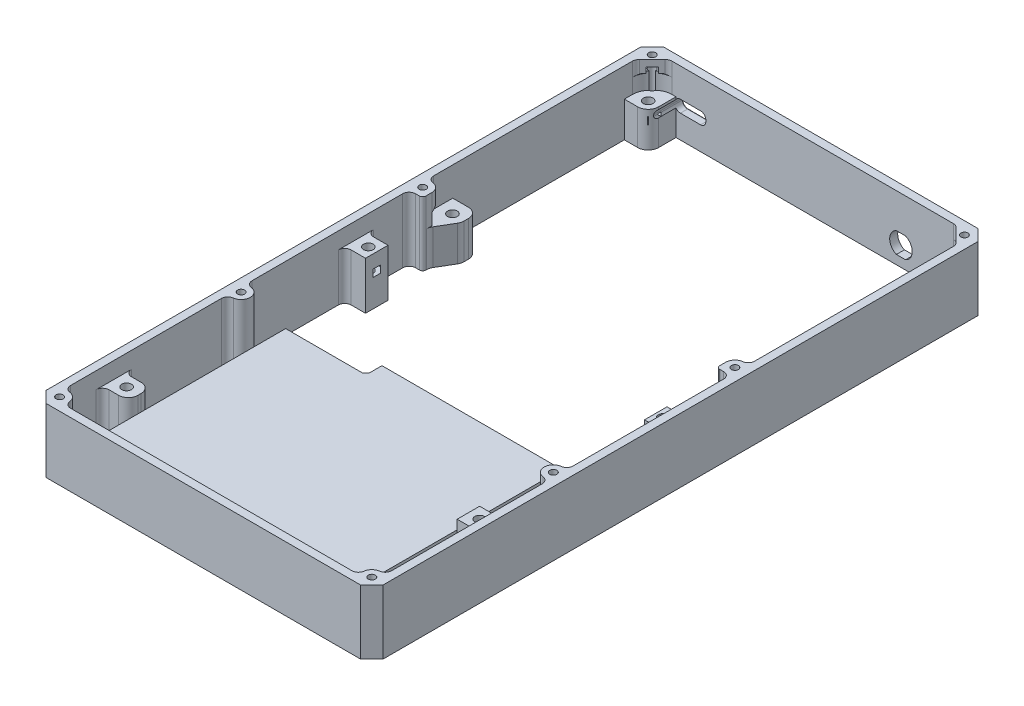
SolidWorks part; units mm, degrees
note: The reader was unsure of these and kept them because the rebuilt part matched: shared geometry of "Sketch1<3>", "Sketch9<3>", "Sketch11<5>".
material "Rubber"
ref_plane "Front Plane" through (0, 0, 0) normal (0, 0, 1) x (1, 0, 0)
ref_plane "Top Plane" through (0, 0, 0) normal (0, 1, 0) x (1, 0, 0)
ref_plane "Right Plane" through (0, 0, 0) normal (1, 0, 0) x (0, 0, -1)
sketch "Sketch1" plane through (0, 0, 0) normal (0, 1, 0) x (1, 0, 0)
  line L0 (0, 0) -> (0, -3.5) construction
  line L1 (0, -3.5) -> (3.5, 0)
  line L2 (3.5, 0) -> (0, 0) construction
  line L3 (3.5, 0) -> (101.5, 0)
  line L4 (101.5, 0) -> (105, -3.5)
  line L5 (105, -3.5) -> (105, -188.8454)
  line L6 (105, -188.8454) -> (101.5, -192.3454)
  line L7 (101.5, -192.3454) -> (3.5, -192.3454)
  line L8 (3.5, -192.3454) -> (0, -188.8454)
  line L9 (0, -188.8454) -> (0, -3.5)
  line L12 (1.75, -1.75) -> (3.8713, -3.8713) construction
  line L13 (103.25, -1.75) -> (101.1287, -3.8713) construction
  line L14 (1.75, -190.5954) -> (3.8713, -188.4741) construction
  line L15 (103.25, -190.5954) -> (101.1287, -188.4741) construction
  line L16 (3.8713, -188.4741) -> (3.8713, -131.9227) construction
  line L17 (3.8713, -131.9227) -> (3.8713, -75.3713) construction
  line L18 (3.8713, -75.3713) -> (3.8713, -3.8713) construction
  line L32 (2.5, -185.9757) -> (2.5, -134.4211)
  line L34 (6.3697, -2.5) -> (98.6303, -2.5)
  line L36 (102.5, -6.3697) -> (102.5, -72.8729)
  line L38 (98.6303, -189.8454) -> (6.3697, -189.8454)
  line L40 (2.5, -187.8099) -> (2.5, -4.5355) construction
  line L41 (4.5355, -189.8454) -> (2.5, -187.8099) construction
  line L42 (100.4645, -189.8454) -> (4.5355, -189.8454) construction
  line L43 (102.5, -187.8099) -> (100.4645, -189.8454) construction
  line L44 (102.5, -4.5355) -> (102.5, -187.8099) construction
  line L45 (102.5, -134.4211) -> (102.5, -185.9757)
  line L46 (102.5, -77.8697) -> (102.5, -129.4243)
  line L47 (2.5, -4.5355) -> (4.5355, -2.5) construction
  line L48 (100.4645, -2.5) -> (102.5, -4.5355) construction
  line L49 (4.5355, -2.5) -> (100.4645, -2.5) construction
  line L50 (2.5, -72.8729) -> (2.5, -6.3697)
  line L51 (2.5, -129.4243) -> (2.5, -77.8697)
  line L52 (52.5, 0) -> (52.5, -192.3454) construction
  line L53 (6.6657, -65.633) -> (2.5, -65.633)
  line L54 (6.7213, -76.1515) -> (10.4157, -69.9096)
  line L55 (98.2787, -76.1515) -> (94.5843, -69.9096)
  line L56 (98.3343, -65.633) -> (102.5, -65.633)
  line L57 (6.6657, -11.173) -> (2.5, -11.173)
  line L58 (98.3343, -11.173) -> (102.5, -11.173)
  line L59 (9.9157, -7.923) -> (9.9157, -2.5)
  line L60 (95.0843, -7.923) -> (95.0843, -2.5)
  line L61 (6.6657, -68.883) -> (9.8928, -70.793) construction
  line L62 (98.3343, -68.883) -> (95.1072, -70.793) construction
  line L63 (94.5843, -69.9096) -> (94.5843, -65.633)
  line L64 (94.5843, -65.633) -> (98.3343, -65.633)
  line L65 (2.5, -64.633) -> (10.4157, -64.633)
  line L66 (10.4157, -69.9096) -> (10.4157, -64.633)
  line L67 (94.5843, -65.633) -> (94.5843, -64.633)
  line L68 (94.5843, -64.633) -> (102.5, -64.633)
  line L69 (98.2787, -76.1515) -> (98.2787, -78.2213)
  line L70 (6.7213, -78.2213) -> (2.5, -78.2213)
  line L71 (6.7213, -76.1515) -> (6.7213, -75.3713)
  line L72 (98.2787, -78.2213) -> (102.5, -78.2213)
  line L73 (6.7213, -76.1515) -> (6.7213, -78.2213)
  line L74 (98.2787, -76.1515) -> (98.2787, -75.3713)
  circle A0 centre (3.8713, -3.8713) radius 1.1
  circle A1 centre (101.1287, -3.8713) radius 1.1
  circle A2 centre (3.8713, -188.4741) radius 1.1
  circle A3 centre (101.1287, -188.4741) radius 1.1
  circle A4 centre (3.8713, -131.9227) radius 1.1
  circle A6 centre (101.1287, -131.9227) radius 1.1
  circle A8 centre (3.8713, -75.3713) radius 1.1
  circle A9 centre (101.1287, -75.3713) radius 1.1
  arc A10 (2.5, -134.4211) -> (2.5, -129.4243) centre (3.8713, -131.9227) ccw
  arc A11 (2.5, -77.8697) -> (2.5, -72.8729) centre (3.8713, -75.3713) ccw
  arc A12 (2.5, -6.3697) -> (6.3697, -2.5) centre (3.8713, -3.8713) ccw
  arc A13 (98.6303, -2.5) -> (102.5, -6.3697) centre (101.1287, -3.8713) ccw
  arc A14 (102.5, -72.8729) -> (102.5, -77.8697) centre (101.1287, -75.3713) ccw
  arc A15 (102.5, -129.4243) -> (102.5, -134.4211) centre (101.1287, -131.9227) ccw
  arc A16 (102.5, -185.9757) -> (98.6303, -189.8454) centre (101.1287, -188.4741) ccw
  arc A17 (6.3697, -189.8454) -> (2.5, -185.9757) centre (3.8713, -188.4741) ccw
  circle A18 centre (3.8713, -188.4741) radius 2.85 construction
  circle A19 centre (101.1287, -188.4741) radius 2.85 construction
  circle A20 centre (101.1287, -131.9227) radius 2.85 construction
  circle A21 centre (101.1287, -75.3713) radius 2.85 construction
  circle A22 centre (101.1287, -3.8713) radius 2.85 construction
  circle A23 centre (3.8713, -3.8713) radius 2.85 construction
  circle A24 centre (3.8713, -75.3713) radius 2.85 construction
  circle A25 centre (3.8713, -131.9227) radius 2.85 construction
  circle A28 centre (6.6657, -68.883) radius 1.5
  circle A29 centre (6.6657, -7.923) radius 1.5
  circle A30 centre (98.3343, -68.883) radius 1.5
  circle A31 centre (98.3343, -7.923) radius 1.5
  circle A32 centre (6.6657, -7.923) radius 3.25
  circle A33 centre (6.6657, -68.883) radius 3.25
  circle A34 centre (98.3343, -68.883) radius 3.25
  circle A35 centre (98.3343, -7.923) radius 3.25
  dimension "D8" = 2.2
  dimension "D9" = 60.96
  dimension "D12" = 3
  dimension "D1" = 3.5
  dimension "D2" = 192.3454
  dimension "D3" = 105
  dimension "D4" = 71.5
  dimension "D5" = 2.5
  dimension "D6" = 1.75
  dimension "D7" = 3
  dimension "D10" = 45.8343
  dimension "D11" = 7.923
  dimension "D13" = 1.75
  dimension "D14" = 1
  dimension "D15" = 1
  dimension "D16" = 3.75
  dimension "D17" = 3.75
  dimension "D18" = 3.75
  dimension "D19" = 3.75
extrude "Boss-Extrude1" add sketch "Sketch1" along normal blind 20
fillet "Fillet1" radius 2 16 edges at (98.6303, 10, 189.8454) (102.5, 10, 185.9757) (102.5, 10, 134.4211) (102.5, 10, 129.4243) (102.5, 10, 72.8729) (102.5, 10, 6.3697) (98.6303, 10, 2.5) (6.3697, 10, 2.5) (2.5, 10, 6.3697) (2.5, 10, 72.8729) (2.5, 10, 129.4243) (2.5, 10, 134.4211) (2.5, 10, 185.9757) (6.3697, 10, 189.8454) (102.5, 10, 78.2213) (2.5, 10, 78.2213)
sketch "Sketch2" plane through (0, 20, 0) normal (0, 1, 0) x (1, 0, 0)
  line L0 (2.9969, -7.361) -> (7.361, -2.9969)
  line L1 (97.639, -2.9969) -> (102.0031, -7.361)
  arc A0 (4.2408, -6.6973) -> (2.5, -8.6804) centre (4.5, -8.6804) ccw construction
  arc A1 (8.6804, -2.5) -> (6.6973, -4.2408) centre (8.6804, -4.5) ccw construction
  arc A2 (4.2408, -6.6973) -> (6.6973, -4.2408) centre (3.8713, -3.8713) ccw construction
  arc A3 (8.6804, -2.5) -> (6.6973, -4.2408) centre (8.6804, -4.5) ccw
  arc A4 (4.2408, -6.6973) -> (6.6973, -4.2408) centre (3.8713, -3.8713) ccw
  arc A5 (4.2408, -6.6973) -> (2.5, -8.6804) centre (4.5, -8.6804) ccw
  arc A6 (98.3027, -4.2408) -> (96.3196, -2.5) centre (96.3196, -4.5) ccw construction
  arc A7 (102.5, -8.6804) -> (100.7592, -6.6973) centre (100.5, -8.6804) ccw construction
  arc A8 (98.3027, -4.2408) -> (100.7592, -6.6973) centre (101.1287, -3.8713) ccw construction
  arc A9 (102.5, -8.6804) -> (100.7592, -6.6973) centre (100.5, -8.6804) ccw
  arc A10 (98.3027, -4.2408) -> (100.7592, -6.6973) centre (101.1287, -3.8713) ccw
  arc A11 (98.3027, -4.2408) -> (96.3196, -2.5) centre (96.3196, -4.5) ccw
extrude "Cut-Extrude1" cut sketch "Sketch2" against normal blind 9
ref_plane "Plane2" through (0, 2.9443, 0) normal (0, -1, 0) x (-1, 0, 0)
sketch "Sketch7" plane through (0, 20, 0) normal (0, 1, 0) x (1, 0, 0)
  line L0 (2.5, -91.5998) -> (102.5, -91.5998)
  line L1 (2.5, -127.1136) -> (2.5, -80.2213) construction
  line L2 (102.5, -80.2213) -> (102.5, -127.1136) construction
extrude "Boss-Extrude2" add sketch "Sketch1<3>" along normal blind 11
sketch "Sketch1<3>" plane through (0, 0, 0) normal (0, 1, 0) x (1, 0, 0) same geometry as "Sketch1"
sketch "Sketch8" plane through (0, 0, 0) normal (0, -1, 0) x (1, 0, 0)
  line L0 (95.5224, 121.923) -> (95.5224, 77.9145) construction
  line L1 (9.4776, 77.9145) -> (9.4776, 121.923) construction
  line L2 (95.5224, 121.923) -> (95.5224, 77.9145) construction
  line L3 (9.4776, 77.9145) -> (9.4776, 121.923) construction
  line L4 (6.4816, 173.7161) -> (2.5, 173.7161)
  line L5 (2.5, 183.665) -> (2.5, 136.7318) construction
  line L6 (6.4816, 166.7161) -> (2.5, 166.7161)
  line L7 (97.1596, 154.4121) -> (102.5, 154.4121)
  line L8 (102.5, 136.7318) -> (102.5, 183.665) construction
  line L9 (97.1596, 147.4121) -> (102.5, 147.4121)
  line L10 (6.3546, 98.2781) -> (2.5, 98.2781)
  line L11 (2.5, 127.1136) -> (2.5, 80.2213) construction
  line L12 (6.3546, 91.2781) -> (2.5, 91.2781)
  line L13 (98.3026, 98.4051) -> (102.5, 98.4051)
  line L14 (102.5, 80.2213) -> (102.5, 127.1136) construction
  line L15 (98.3026, 91.4051) -> (102.5, 91.4051)
  line L16 (96.0224, 97.5604) -> (96.0224, 92.2498)
  line L17 (2.5, 98.2781) -> (2.5, 91.2781)
  line L18 (102.5, 98.4051) -> (102.5, 91.4051)
  line L19 (102.5, 154.4121) -> (102.5, 147.4121)
  line L20 (2.5, 173.7161) -> (2.5, 166.7161)
  line L21 (96.0224, 92.2498) -> (96.0224, 91.4051)
  line L22 (96.0224, 91.4051) -> (98.3026, 91.4051)
  line L23 (96.0224, 97.5604) -> (96.0224, 98.4051)
  line L24 (96.0224, 98.4051) -> (98.3026, 98.4051)
  line L25 (97.1596, 147.4121) -> (93.6596, 147.4121)
  line L26 (93.6596, 147.4121) -> (93.6596, 154.4121)
  line L27 (93.6596, 154.4121) -> (97.1596, 154.4121)
  line L28 (6.4816, 166.7161) -> (10.5, 166.7161)
  line L29 (10.5, 166.7161) -> (10.5, 173.7161)
  line L30 (10.5, 173.7161) -> (6.4816, 173.7161)
  line L31 (6.3546, 91.2781) -> (8.9776, 91.2781)
  line L33 (8.9776, 91.2781) -> (8.9776, 98.2781)
  line L34 (8.9776, 98.2781) -> (6.3546, 98.2781)
  circle A0 centre (98.3026, 94.9051) radius 1.5 construction
  circle A1 centre (6.3546, 94.7781) radius 1.5 construction
  circle A2 centre (97.1596, 150.9121) radius 1.5 construction
  circle A3 centre (6.4816, 170.2161) radius 1.5 construction
  circle A4 centre (98.3026, 94.9051) radius 1.5 construction
  circle A5 centre (6.3546, 94.7781) radius 1.5 construction
  circle A6 centre (97.1596, 150.9121) radius 1.5 construction
  circle A7 centre (6.4816, 170.2161) radius 1.5 construction
  circle A8 centre (6.4816, 170.2161) radius 3.5 construction
  circle A9 centre (97.1596, 150.9121) radius 3.5 construction
  circle A10 centre (98.3026, 94.9051) radius 3.5
  circle A11 centre (6.3546, 94.7781) radius 3.5 construction
  circle A12 centre (6.4816, 170.2161) radius 1.5
  circle A13 centre (97.1596, 150.9121) radius 1.5
  circle A14 centre (98.3026, 94.9051) radius 1.5
  circle A15 centre (6.3546, 94.7781) radius 1.5
  dimension "D1" = 7
  dimension "D2" = 3
  dimension "D3" = 0.5
  dimension "D4" = 8
  dimension "D5" = 0.5
extrude "Boss-Extrude3" add sketch "Sketch8" against normal blind 14.86 contours A8 L4 L20 L6 | A8 A12 | A9 A13 | A9 L9 L19 L7 | A11 L10 L17 L12 | A11 A15 | A10 L16 A14 | A10 L15 L18 L13 | A10 L24 L23 | A10 L21 L22
fillet "Fillet2" radius 2 8 edges at (2.5, 7.43, 98.2781) (2.5, 7.43, 91.2781) (102.5, 7.43, 98.4051) (102.5, 7.43, 91.4051) (102.5, 7.43, 154.4121) (102.5, 7.43, 147.4121) (2.5, 7.43, 166.7161) (2.5, 7.43, 173.7161)
sketch "Sketch9" plane through (0, 0, 0) normal (0, -1, 0) x (1, 0, 0)
  line L0 (96.3196, 189.8454) -> (8.6804, 189.8454) construction
  line L1 (53.6596, 189.8454) -> (52.6596, 189.8454)
  line L2 (53.6596, 189.8454) -> (53.6596, 127.8454)
  line L3 (53.6596, 127.8454) -> (52.6596, 127.8454)
  line L4 (52.6596, 189.8454) -> (52.6596, 127.8454)
  line L5 (93.6596, 189.8454) -> (93.6596, 121.8454)
  line L6 (93.6596, 121.8454) -> (37.6596, 121.8454)
  line L7 (92.6596, 189.8454) -> (92.6596, 127.8454)
  line L8 (84.6596, 122.8454) -> (37.6596, 122.8454)
  line L9 (92.6596, 127.8454) -> (84.6596, 127.8454)
  line L10 (84.6596, 127.8454) -> (84.6596, 122.8454)
  line L11 (12.6596, 189.8454) -> (12.6596, 126.8454)
  line L12 (12.6596, 126.8454) -> (13.6596, 126.8454)
  line L13 (21.6596, 126.8454) -> (21.6596, 127.8454) construction
  line L14 (21.6596, 127.8454) -> (13.6596, 127.8454) construction
  line L15 (13.6596, 127.8454) -> (13.6596, 189.8454)
  line L16 (37.6596, 122.8454) -> (37.6596, 121.8454)
  line L17 (92.6596, 189.8454) -> (93.6596, 189.8454)
  line L18 (12.6596, 189.8454) -> (13.6596, 189.8454)
  line L19 (12.6596, 189.8454) -> (93.6596, 189.8454)
  line L20 (21.6596, 126.8454) -> (37.6596, 126.8454)
  line L21 (37.6596, 126.8454) -> (37.6596, 122.8454)
  line L22 (13.6596, 127.8454) -> (13.6596, 126.8454)
  line L23 (44.6596, 126.8454) -> (61.6596, 126.8454)
  line L24 (44.6596, 126.8454) -> (44.6596, 127.8454)
  line L25 (44.6596, 127.8454) -> (61.6596, 127.8454)
  line L26 (61.6596, 126.8454) -> (61.6596, 127.8454)
  line L27 (13.6596, 126.8454) -> (21.6596, 126.8454)
  line L28 (12.6596, 136.8454) -> (13.6596, 136.8454)
  line L29 (12.6596, 126.8454) -> (2.5, 126.8454)
  line L30 (2.5, 127.1136) -> (2.5, 100.2781) construction
  line L31 (102.5, 100.4051) -> (102.5, 127.1136) construction
  line L32 (102.5, 136.7318) -> (102.5, 145.4121) construction
  line L33 (93.6596, 147.4121) -> (100.5, 147.4121) construction
  line L34 (93.6596, 154.4121) -> (100.5, 154.4121) construction
  line L35 (102.5, 156.4121) -> (102.5, 183.665) construction
  line L36 (2.5, 183.665) -> (2.5, 175.7161) construction
  line L37 (10.5, 173.7161) -> (4.5, 173.7161) construction
  line L38 (2.5, 164.7161) -> (2.5, 136.7318) construction
  line L39 (10.5, 166.7161) -> (4.5, 166.7161) construction
  line L40 (102.5, 100.4051) -> (102.5, 127.1136)
  line L41 (2.5, 127.1136) -> (2.5, 100.2781)
  line L42 (102.5, 136.7318) -> (102.5, 145.4121)
  line L43 (93.6596, 147.4121) -> (100.5, 147.4121)
  line L44 (93.6596, 154.4121) -> (100.5, 154.4121)
  line L45 (102.5, 156.4121) -> (102.5, 183.665)
  line L46 (96.3196, 189.8454) -> (8.6804, 189.8454)
  line L47 (2.5, 183.665) -> (2.5, 175.7161)
  line L48 (10.5, 173.7161) -> (4.5, 173.7161)
  line L49 (2.5, 164.7161) -> (2.5, 136.7318)
  line L50 (10.5, 166.7161) -> (4.5, 166.7161)
  line L51 (93.6596, 121.8454) -> (102.5, 121.8454)
  line L52 (13.6596, 187.8454) -> (52.6596, 187.8454)
  line L53 (53.6596, 187.8454) -> (92.6596, 187.8454)
  arc A2 (4.2408, 129.0967) -> (2.5, 127.1136) centre (4.5, 127.1136) ccw construction
  arc A3 (4.2408, 129.0967) -> (4.2408, 134.7487) centre (3.8713, 131.9227) ccw construction
  arc A4 (2.5, 136.7318) -> (4.2408, 134.7487) centre (4.5, 136.7318) ccw construction
  arc A5 (102.5, 127.1136) -> (100.7592, 129.0967) centre (100.5, 127.1136) ccw construction
  arc A6 (100.7592, 134.7487) -> (100.7592, 129.0967) centre (101.1287, 131.9227) ccw construction
  arc A7 (100.7592, 134.7487) -> (102.5, 136.7318) centre (100.5, 136.7318) ccw construction
  arc A8 (102.5, 145.4121) -> (100.5, 147.4121) centre (100.5, 145.4121) ccw construction
  arc A10 (100.5, 154.4121) -> (102.5, 156.4121) centre (100.5, 156.4121) ccw construction
  arc A11 (102.5, 183.665) -> (100.7592, 185.6481) centre (100.5, 183.665) ccw construction
  arc A12 (98.3027, 188.1046) -> (100.7592, 185.6481) centre (101.1287, 188.4741) ccw construction
  arc A13 (98.3027, 188.1046) -> (96.3196, 189.8454) centre (96.3196, 187.8454) ccw construction
  arc A14 (8.6804, 189.8454) -> (6.6973, 188.1046) centre (8.6804, 187.8454) ccw construction
  arc A15 (4.2408, 185.6481) -> (6.6973, 188.1046) centre (3.8713, 188.4741) ccw construction
  arc A16 (4.2408, 185.6481) -> (2.5, 183.665) centre (4.5, 183.665) ccw construction
  arc A17 (2.5, 175.7161) -> (4.5, 173.7161) centre (4.5, 175.7161) ccw construction
  arc A18 (4.5, 166.7161) -> (2.5, 164.7161) centre (4.5, 164.7161) ccw construction
  arc A19 (4.2408, 129.0967) -> (2.5, 127.1136) centre (4.5, 127.1136) ccw
  arc A20 (4.2408, 129.0967) -> (4.2408, 134.7487) centre (3.8713, 131.9227) ccw
  arc A21 (2.5, 136.7318) -> (4.2408, 134.7487) centre (4.5, 136.7318) ccw
  arc A22 (102.5, 127.1136) -> (100.7592, 129.0967) centre (100.5, 127.1136) ccw
  arc A23 (100.7592, 134.7487) -> (100.7592, 129.0967) centre (101.1287, 131.9227) ccw
  arc A24 (100.7592, 134.7487) -> (102.5, 136.7318) centre (100.5, 136.7318) ccw
  arc A25 (102.5, 145.4121) -> (100.5, 147.4121) centre (100.5, 145.4121) ccw
  arc A27 (100.5, 154.4121) -> (102.5, 156.4121) centre (100.5, 156.4121) ccw
  arc A28 (102.5, 183.665) -> (100.7592, 185.6481) centre (100.5, 183.665) ccw
  arc A29 (98.3027, 188.1046) -> (100.7592, 185.6481) centre (101.1287, 188.4741) ccw
  arc A30 (98.3027, 188.1046) -> (96.3196, 189.8454) centre (96.3196, 187.8454) ccw
  arc A31 (8.6804, 189.8454) -> (6.6973, 188.1046) centre (8.6804, 187.8454) ccw
  arc A32 (4.2408, 185.6481) -> (6.6973, 188.1046) centre (3.8713, 188.4741) ccw
  arc A33 (4.2408, 185.6481) -> (2.5, 183.665) centre (4.5, 183.665) ccw
  arc A34 (2.5, 175.7161) -> (4.5, 173.7161) centre (4.5, 175.7161) ccw
  arc A35 (4.5, 166.7161) -> (2.5, 164.7161) centre (4.5, 164.7161) ccw
  point P21 (53.1596, 127.8454)
  point P27 (53.1596, 127.8454)
  dimension "D1" = 39
  dimension "D2" = 39
  dimension "D3" = 1
  dimension "D4" = 62
  dimension "D5" = 68
  dimension "D6" = 8
  dimension "D7" = 8
  dimension "D8" = 25
  dimension "D9" = 10
extrude "Boss-Extrude4" add sketch "Sketch9" against normal blind 12 contours L17 L7 L9 L10 L8 L16 L6 L5 | L1 L4 L3 L2 | L18 L11 L12 L13 L14 L15 | L23 L26 L25 L3 L24
extrude "Boss-Extrude5" add sketch "Sketch9<3>" along normal blind 1 from surface at -12 starting at face at (53.1596, 12, 143.0954)
sketch "Sketch9<3>" plane through (0, 0, 0) normal (0, -1, 0) x (1, 0, 0) same geometry as "Sketch9"
chamfer "Chamfer1" distance 1 angle 45 4 edges at (93.6596, 6, 189.8454) (84.6596, 5.5, 127.8454) (84.6596, 5.5, 122.8454) (37.6596, 11.5, 126.8454)
sketch "Sketch10" plane through (0, 0, 0) normal (0, -1, 0) x (1, 0, 0)
  line L1 (4.5064, 186.104) -> (6.2414, 187.839)
  line L2 (6.2414, 187.839) -> (5.6064, 190.2091)
  line L3 (5.6064, 190.2091) -> (3.2362, 190.8442)
  line L4 (3.2362, 190.8442) -> (1.5012, 189.1092)
  line L5 (1.5012, 189.1092) -> (2.1363, 186.739)
  line L6 (2.1363, 186.739) -> (4.5064, 186.104)
  line L7 (105, 188.8454) -> (101.5, 192.3454) construction
  line L8 (3.5, 192.3454) -> (0, 188.8454) construction
  line L9 (2.1363, 186.739) -> (4.9917, 183.8836)
  line L11 (102.8637, 186.739) -> (103.4988, 189.1092)
  line L12 (103.4988, 189.1092) -> (101.7638, 190.8442)
  line L13 (101.7638, 190.8442) -> (99.3936, 190.2091)
  line L14 (99.3936, 190.2091) -> (98.7586, 187.839)
  line L15 (98.7586, 187.839) -> (100.4936, 186.104)
  line L16 (100.4936, 186.104) -> (102.8637, 186.739)
  line L17 (8.4618, 187.3537) -> (5.6064, 190.2091)
  line L18 (99.3936, 190.2091) -> (95.2942, 186.1097)
  line L21 (6.3251, 131.9227) -> (5.0982, 134.0477)
  line L22 (5.0982, 134.0477) -> (2.6445, 134.0477)
  line L23 (2.6445, 134.0477) -> (1.4176, 131.9227)
  line L24 (1.4176, 131.9227) -> (2.6445, 129.7977)
  line L25 (2.6445, 129.7977) -> (5.0982, 129.7977)
  line L26 (5.0982, 129.7977) -> (6.3251, 131.9227)
  line L27 (98.6749, 131.9227) -> (99.9018, 129.7977)
  line L28 (99.9018, 129.7977) -> (102.3555, 129.7977)
  line L29 (102.3555, 129.7977) -> (103.5824, 131.9227)
  line L30 (103.5824, 131.9227) -> (102.3555, 134.0477)
  line L31 (102.3555, 134.0477) -> (99.9018, 134.0477)
  line L32 (99.9018, 134.0477) -> (98.6749, 131.9227)
  line L33 (98.6749, 75.3713) -> (99.9018, 73.2463)
  line L34 (99.9018, 73.2463) -> (102.3555, 73.2463)
  line L35 (102.3555, 73.2463) -> (103.5824, 75.3713)
  line L36 (103.5824, 75.3713) -> (102.3555, 77.4963)
  line L37 (102.3555, 77.4963) -> (99.9018, 77.4963)
  line L38 (99.9018, 77.4963) -> (98.6749, 75.3713)
  line L39 (6.3251, 75.3713) -> (5.0982, 77.4963)
  line L40 (5.0982, 77.4963) -> (2.6445, 77.4963)
  line L41 (2.6445, 77.4963) -> (1.4176, 75.3713)
  line L42 (1.4176, 75.3713) -> (2.6445, 73.2463)
  line L43 (2.6445, 73.2463) -> (5.0982, 73.2463)
  line L44 (5.0982, 73.2463) -> (6.3251, 75.3713)
  line L45 (5.6064, 2.1363) -> (6.2414, 4.5064)
  line L46 (6.2414, 4.5064) -> (4.5064, 6.2414)
  line L47 (4.5064, 6.2414) -> (2.1363, 5.6064)
  line L48 (2.1363, 5.6064) -> (1.5012, 3.2362)
  line L49 (1.5012, 3.2362) -> (3.2362, 1.5012)
  line L50 (3.2362, 1.5012) -> (5.6064, 2.1363)
  line L51 (99.3936, 2.1363) -> (101.7638, 1.5012)
  line L52 (101.7638, 1.5012) -> (103.4988, 3.2362)
  line L53 (103.4988, 3.2362) -> (102.8637, 5.6064)
  line L54 (102.8637, 5.6064) -> (100.4936, 6.2414)
  line L55 (100.4936, 6.2414) -> (98.7586, 4.5064)
  line L56 (98.7586, 4.5064) -> (99.3936, 2.1363)
  line L58 (0, 3.5) -> (3.5, 0) construction
  line L59 (2.1363, 5.6064) -> (9.0446, 12.5147)
  line L61 (101.5, 0) -> (105, 3.5) construction
  line L62 (99.3936, 2.1363) -> (92.9674, 8.5625)
  line L64 (99.9018, 73.2463) -> (92.3774, 73.2463)
  line L66 (92.3774, 77.4963) -> (99.9018, 77.4963)
  line L67 (5.0982, 77.4963) -> (9.8005, 77.4963)
  line L69 (9.8005, 73.2463) -> (5.0982, 73.2463)
  line L70 (99.9018, 129.7977) -> (95.2942, 129.7977)
  line L72 (95.2942, 134.0477) -> (99.9018, 134.0477)
  line L73 (5.0982, 134.0477) -> (7.5202, 134.0477)
  line L75 (7.5202, 129.7977) -> (5.0982, 129.7977)
  line L77 (12.5147, 9.0446) -> (5.6064, 2.1363)
  line L78 (96.4375, 12.0326) -> (102.8637, 5.6064)
  line L80 (98.862, 182.7373) -> (102.8637, 186.739)
  circle A0 centre (3.8713, 188.4741) radius 2.125 construction
  circle A1 centre (101.1287, 188.4741) radius 2.125 construction
  circle A2 centre (3.8713, 131.9227) radius 2.125 construction
  circle A3 centre (101.1287, 131.9227) radius 2.125 construction
  circle A4 centre (101.1287, 75.3713) radius 2.125 construction
  circle A5 centre (3.8713, 75.3713) radius 2.125 construction
  circle A6 centre (3.8713, 3.8713) radius 2.125 construction
  circle A7 centre (101.1287, 3.8713) radius 2.125 construction
  dimension "D1" = 4.25
extrude "Cut-Extrude3" cut sketch "Sketch10" against normal blind 1.75 from offset 2 offset against normal yes
ref_plane "Midplane" through (0, 10, 0) normal (0, -1, 0) x (-1, 0, 0)
mirror "Mirror1" about plane through (0, 10, 0) normal (0, -1, 0) of "Cut-Extrude3"
sketch "Sketch11" plane through (0, 20, 0) normal (0, 1, 0) x (1, 0, 0)
  line L0 (0, -3.5) -> (3.5, 0) construction
  line L1 (5.8065, -11.1296) -> (9.0131, -10.2704)
  line L2 (9.0131, -10.2704) -> (9.8723, -7.0638)
  line L3 (9.8723, -7.0638) -> (7.5249, -4.7164)
  line L4 (7.5249, -4.7164) -> (4.3183, -5.5756)
  line L5 (4.3183, -5.5756) -> (3.4591, -8.7822)
  line L6 (3.4591, -8.7822) -> (5.8065, -11.1296)
  line L7 (99.1935, -11.1296) -> (101.5409, -8.7822)
  line L8 (101.5409, -8.7822) -> (100.6817, -5.5756)
  line L9 (100.6817, -5.5756) -> (97.4751, -4.7164)
  line L10 (97.4751, -4.7164) -> (95.1277, -7.0638)
  line L11 (95.1277, -7.0638) -> (95.9869, -10.2704)
  line L12 (95.9869, -10.2704) -> (99.1935, -11.1296)
  line L13 (3.3459, -68.883) -> (5.0058, -71.758)
  line L14 (5.0058, -71.758) -> (8.3256, -71.758)
  line L15 (8.3256, -71.758) -> (9.9855, -68.883)
  line L16 (9.9855, -68.883) -> (8.3256, -66.008)
  line L17 (8.3256, -66.008) -> (5.0058, -66.008)
  line L18 (5.0058, -66.008) -> (3.3459, -68.883)
  line L19 (101.6541, -68.883) -> (99.9942, -66.008)
  line L20 (99.9942, -66.008) -> (96.6744, -66.008)
  line L21 (96.6744, -66.008) -> (95.0145, -68.883)
  line L22 (95.0145, -68.883) -> (96.6744, -71.758)
  line L23 (96.6744, -71.758) -> (99.9942, -71.758)
  line L24 (99.9942, -71.758) -> (101.6541, -68.883)
  line L25 (4.6947, -97.6531) -> (8.0145, -97.6531)
  line L26 (8.0145, -97.6531) -> (9.6744, -94.7781)
  line L27 (9.6744, -94.7781) -> (8.0145, -91.9031)
  line L28 (8.0145, -91.9031) -> (4.6947, -91.9031)
  line L29 (4.6947, -91.9031) -> (3.0348, -94.7781)
  line L30 (3.0348, -94.7781) -> (4.6947, -97.6531)
  line L31 (101.6224, -94.9051) -> (99.9625, -92.0301)
  line L32 (99.9625, -92.0301) -> (96.6427, -92.0301)
  line L33 (96.6427, -92.0301) -> (94.9828, -94.9051)
  line L34 (94.9828, -94.9051) -> (96.6427, -97.7801)
  line L35 (96.6427, -97.7801) -> (99.9625, -97.7801)
  line L36 (99.9625, -97.7801) -> (101.6224, -94.9051)
  line L37 (8.1415, -167.3411) -> (4.8217, -167.3411)
  line L38 (4.8217, -167.3411) -> (3.1618, -170.2161)
  line L39 (3.1618, -170.2161) -> (4.8217, -173.0911)
  line L40 (4.8217, -173.0911) -> (8.1415, -173.0911)
  line L41 (8.1415, -173.0911) -> (9.8014, -170.2161)
  line L42 (9.8014, -170.2161) -> (8.1415, -167.3411)
  line L43 (95.4997, -148.0371) -> (93.8398, -150.9121)
  line L44 (93.8398, -150.9121) -> (95.4997, -153.7871)
  line L45 (95.4997, -153.7871) -> (98.8195, -153.7871)
  line L46 (98.8195, -153.7871) -> (100.4794, -150.9121)
  line L47 (100.4794, -150.9121) -> (98.8195, -148.0371)
  line L48 (98.8195, -148.0371) -> (95.4997, -148.0371)
  line L49 (101.5, 0) -> (105, -3.5) construction
  line L51 (5.8065, -11.1296) -> (8.515, -13.8382)
  line L53 (12.5809, -9.7723) -> (9.8723, -7.0638)
  line L54 (95.1277, -7.0638) -> (91.4185, -10.7729)
  line L56 (95.4844, -14.8388) -> (99.1935, -11.1296)
  line L57 (8.3256, -66.008) -> (14.5408, -66.008)
  line L59 (14.5408, -71.758) -> (8.3256, -71.758)
  line L60 (96.6744, -66.008) -> (92.8765, -66.008)
  line L62 (92.8765, -71.758) -> (96.6744, -71.758)
  line L63 (8.0145, -91.9031) -> (12.1856, -91.9031)
  line L65 (12.1856, -97.6531) -> (8.0145, -97.6531)
  line L66 (96.6427, -92.0301) -> (91.9804, -92.0301)
  line L68 (91.9804, -97.7801) -> (96.6427, -97.7801)
  line L69 (8.1415, -167.3411) -> (13.132, -167.3411)
  line L71 (13.132, -173.0911) -> (8.1415, -173.0911)
  line L72 (95.4997, -148.0371) -> (90.6077, -148.0371)
  line L74 (90.6077, -153.7871) -> (95.4997, -153.7871)
  line L75 (94.5843, -64.633) -> (102.5, -64.633) construction
  circle A0 centre (6.6657, -7.923) radius 2.875 construction
  circle A1 centre (98.3343, -7.923) radius 2.875 construction
  circle A2 centre (6.6657, -68.883) radius 2.875 construction
  circle A3 centre (98.3343, -68.883) radius 2.875 construction
  circle A4 centre (6.3546, -94.7781) radius 2.875 construction
  circle A5 centre (98.3026, -94.9051) radius 2.875 construction
  circle A6 centre (6.4816, -170.2161) radius 2.875 construction
  circle A7 centre (97.1596, -150.9121) radius 2.875 construction
  dimension "D1" = 5.75
extrude "Cut-Extrude4" cut sketch "Sketch11" against normal blind 2.25 from offset 11 offset against normal yes
sketch "Sketch12" plane through (0, 0, 0) normal (0, 0, -1) x (-1, 0, 0)
  line L0 (-11.2906, 10.7222) -> (-14.0756, 10.7222) construction
  line L1 (-18.9106, 8.8922) -> (-18.9106, 9.3922) construction
  line L2 (-9.9606, 8.8922) -> (-9.9606, 9.3922) construction
  line L3 (-11.2906, 7.5622) -> (-17.5806, 7.5622) construction
  line L4 (-11.2906, 10.7222) -> (-14.0756, 10.7222) construction
  line L5 (-18.9106, 8.8922) -> (-18.9106, 9.3922) construction
  line L6 (-9.9606, 8.8922) -> (-9.9606, 9.3922) construction
  line L7 (-11.2906, 7.5622) -> (-17.5806, 7.5622) construction
  line L8 (-14.0756, 10.7222) -> (-17.5806, 10.7222) construction
  line L9 (-14.0756, 11.0222) -> (-17.5806, 11.0222)
  line L10 (-19.2106, 8.8922) -> (-19.2106, 9.3922)
  line L11 (-11.2906, 7.2622) -> (-17.5806, 7.2622)
  line L12 (-9.6606, 8.8922) -> (-9.6606, 9.3922)
  line L13 (-11.2906, 11.0222) -> (-14.0756, 11.0222)
  line L15 (-105, 20) -> (-105, 0) construction
  line L16 (-3.5, 0) -> (-101.5, 0) construction
  line L18 (-81.432, 9.2115) -> (-78.568, 9.2115)
  line L19 (-81.432, 9.2115) -> (-81.432, 2.7885) construction
  line L20 (-81.432, 2.7885) -> (-78.568, 2.7885)
  line L21 (-78.568, 9.2115) -> (-78.568, 2.7885) construction
  arc A0 (-18.9106, 8.8922) -> (-17.5806, 7.5622) centre (-17.5806, 8.8922) ccw construction
  arc A1 (-11.2906, 7.5622) -> (-9.9606, 8.8922) centre (-11.2906, 8.8922) ccw construction
  arc A2 (-9.9606, 9.3922) -> (-11.2906, 10.7222) centre (-11.2906, 9.3922) ccw construction
  arc A3 (-17.5806, 10.7222) -> (-18.9106, 9.3922) centre (-17.5806, 9.3922) ccw construction
  arc A4 (-17.5806, 11.0222) -> (-19.2106, 9.3922) centre (-17.5806, 9.3922) ccw
  arc A5 (-19.2106, 8.8922) -> (-17.5806, 7.2622) centre (-17.5806, 8.8922) ccw
  arc A6 (-11.2906, 7.2622) -> (-9.6606, 8.8922) centre (-11.2906, 8.8922) ccw
  arc A7 (-9.6606, 9.3922) -> (-11.2906, 11.0222) centre (-11.2906, 9.3922) ccw
  circle A8 centre (-80, 6) radius 3.5163
  dimension "D2" = 7.0326
  dimension "D3" = 6
  dimension "D4" = 25
  dimension "D5" = 6.423
  dimension "D1" = 0.3
extrude "Cut-Extrude6" cut sketch "Sketch12" against normal up to next contours L18 A8 L20 | L12 A7 L13 L9 A4 L10 A5 L11 A6
fillet "Fillet3" radius 0.3 8 edges at (18.7331, 7.7396, 0) (19.2106, 9.1422, 0) (18.7331, 10.5448, 0) (14.4356, 11.0222, 0) (10.138, 10.5448, 0) (9.6606, 9.1422, 0) (10.138, 7.7396, 0) (14.4356, 7.2622, 0)
sketch "Sketch13" plane through (0, 20, 0) normal (0, 1, 0) x (1, 0, 0)
  line L0 (100.1378, -4.0816) -> (100.9184, -4.8622)
  line L1 (102.5, -8.6804) -> (102.5, -70.5622) construction
  line L2 (8.6804, -2.5) -> (96.3196, -2.5) construction
  line L3 (97.8227, -3.1806) -> (101.8194, -7.1773) construction
  line L4 (97.8227, -3.1806) -> (101.8194, -7.1773)
  line L5 (52.5, 0) -> (52.5, -2.5) construction
  line L6 (3.5, 0) -> (101.5, 0) construction
  line L7 (4.8622, -4.0816) -> (4.0816, -4.8622)
  line L8 (7.1773, -3.1806) -> (3.1806, -7.1773)
  arc A0 (102.5, -8.6804) -> (101.8194, -7.1773) centre (100.5, -8.6804) ccw construction
  arc A1 (97.8227, -3.1806) -> (96.3196, -2.5) centre (96.3196, -4.5) ccw construction
  arc A2 (102.5, -8.6804) -> (101.8194, -7.1773) centre (100.5, -8.6804) ccw
  arc A3 (97.8227, -3.1806) -> (96.3196, -2.5) centre (96.3196, -4.5) ccw
  arc A4 (96.3196, -2.5) -> (100.1378, -4.0816) centre (96.3196, -7.8998) cw
  arc A5 (100.9184, -4.8622) -> (102.5, -8.6804) centre (97.1002, -8.6804) cw
  arc A6 (4.0816, -4.8622) -> (2.5, -8.6804) centre (7.8998, -8.6804) ccw
  arc A7 (2.5, -8.6804) -> (3.1806, -7.1773) centre (4.5, -8.6804) cw
  arc A8 (7.1773, -3.1806) -> (8.6804, -2.5) centre (8.6804, -4.5) cw
  arc A9 (8.6804, -2.5) -> (4.8622, -4.0816) centre (8.6804, -7.8998) ccw
  dimension "D1" = 1
extrude "Cut-Extrude7" cut sketch "Sketch13" against normal up to surface (5.25 mm away) from surface at -3.75 up to face at (6.3716, 11, 6.8431) starting at face at (3.8713, 16.25, 4.9713)
chamfer "Chamfer3" distance 0.6 angle 45 4 edges at (7.2428, 16.25, 2.6949) (2.6949, 16.25, 7.2428) (102.3051, 16.25, 7.2428) (97.7572, 16.25, 2.6949)
ref_plane "Plane3" through (52.5, 0, 0) normal (-1, 0, 0) x (0, 0, 1)
sketch "Sketch16" plane through (0, 20, 0) normal (0, 1, 0) x (1, 0, 0)
  line L6 (3.1353, -72.0243) -> (6.7213, -75.3713)
  line L7 (98.2787, -75.3713) -> (101.8647, -72.0243)
  line L8 (6.7213, -75.3713) -> (6.7213, -78.2213) construction
  line L9 (6.7213, -75.3713) -> (6.7213, -78.2213)
  line L10 (98.2787, -78.2213) -> (98.2787, -75.3713) construction
  line L11 (98.2787, -78.2213) -> (98.2787, -75.3713)
  arc A0 (100.7592, -72.5454) -> (102.5, -70.5622) centre (100.5, -70.5622) ccw construction
  arc A1 (2.5, -70.5622) -> (4.2408, -72.5454) centre (4.5, -70.5622) ccw construction
  arc A2 (100.7592, -72.5454) -> (102.5, -70.5622) centre (100.5, -70.5622) ccw
  arc A3 (2.5, -70.5622) -> (4.2408, -72.5454) centre (4.5, -70.5622) ccw
  arc A9 (6.7213, -75.3713) -> (4.2408, -72.5454) centre (3.8713, -75.3713) ccw construction
  arc A10 (6.7213, -75.3713) -> (4.2408, -72.5454) centre (3.8713, -75.3713) ccw
  arc A13 (100.7592, -72.5454) -> (98.2787, -75.3713) centre (101.1287, -75.3713) ccw construction
  arc A14 (100.7592, -72.5454) -> (98.2787, -75.3713) centre (101.1287, -75.3713) ccw
extrude "Cut-Extrude19" cut sketch "Sketch16" along normal blind 5 from surface at -9
chamfer "Chamfer5" distance 1.4 angle 45 2 edges at (4.9283, 16, 73.6978) (100.0717, 16, 73.6978)
extrude "Cut-Extrude20" cut sketch "Sketch11<5>" against normal blind 2.25 from offset 9.25 contours L35 L36 L31 L32 L33 L34 | L29 L30 L25 L26 L27 L28 | L41 L42 L37 L38 L39 L40 | L47 L48 L43 L44 L45 L46 offset against normal yes
sketch "Sketch11<5>" plane through (0, 20, 0) normal (0, 1, 0) x (1, 0, 0) same geometry as "Sketch11"
fillet "Fillet4" radius 3 8 edges at (98.2787, 5.5, 76.1515) (94.5843, 5.5, 69.9096) (6.7213, 5.5, 76.1515) (10.4157, 5.5, 69.9096) (10.4157, 5.5, 64.633) (94.5843, 5.5, 64.633) (10.5, 7.43, 166.7161) (10.5, 7.43, 173.7161)
fillet "Fillet5" radius 1 2 edges at (98.2787, 10, 78.2213) (6.7213, 10, 78.2213)
